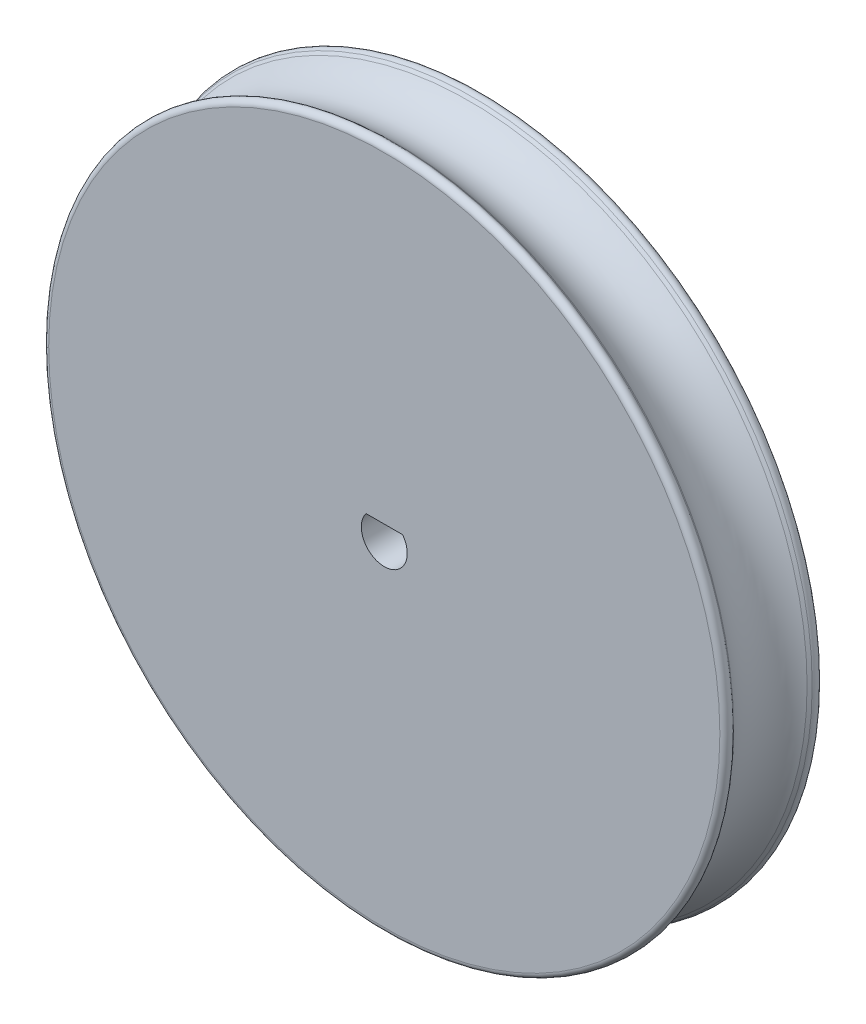
SolidWorks part; units mm, degrees
ref_plane "Front Plane" through (0, 0, 0) normal (0, 0, 1) x (1, 0, 0)
ref_plane "Top Plane" through (0, 0, 0) normal (0, 1, 0) x (1, 0, 0)
ref_plane "Right Plane" through (0, 0, 0) normal (1, 0, 0) x (0, 0, -1)
sketch "Sketch1" plane through (0, 0, 0) normal (0, 0, 1) x (1, 0, 0)
  circle A0 centre (0, 0) radius 1.5
  circle A1 centre (0, 0) radius 25
  dimension "D1" = 3
  dimension "D2" = 50
extrude "Boss-Extrude1" add sketch "Sketch1" along normal blind 7
sketch "Sketch2" plane through (0, 0, 0) normal (1, 0, 0) x (0, 0, -1)
  line L0 (-7, 25) -> (-6.1399, 24.237)
  line L1 (0, 25) -> (-0.8601, 24.237)
  line L2 (-7, 25) -> (0, 25)
  line L3 (-3.5, 25) -> (-3.5, 22.4442) construction
  arc A0 (-6.1399, 24.237) -> (-0.8601, 24.237) centre (-3.5, 26.7401) ccw
  point P7 (-6.1122, 24.4309)
  point P10 (-6.1399, 24.237)
ref_axis "Axis1" through (0, 0, 7) along (0, 0, -1)
revolve "Cut-Revolve1" cut sketch "Sketch2" angle 360 about axis through (0, 0, 7) along (0, 0, -1)
fillet "Fillet1" radius 0.4 2 edges at (25, 0, 0) (25, 0, 7)
sketch "Sketch3" plane through (0, 0, 7) normal (0, 0, 1) x (1, 0, 0)
  line L0 (-1.12, 0.9978) -> (1.12, 0.9978)
  circle A0 centre (0, 0) radius 1.5 construction
  arc A1 (1.12, 0.9978) -> (-1.12, 0.9978) centre (0, 0) ccw
  dimension "D1" = 2.24
extrude "Boss-Extrude2" add sketch "Sketch3" against normal through all
other "Move Face1" flip direction yes face at (0, -0.2511, 3.5) offset 0.15 parameters "D1"=0.15
